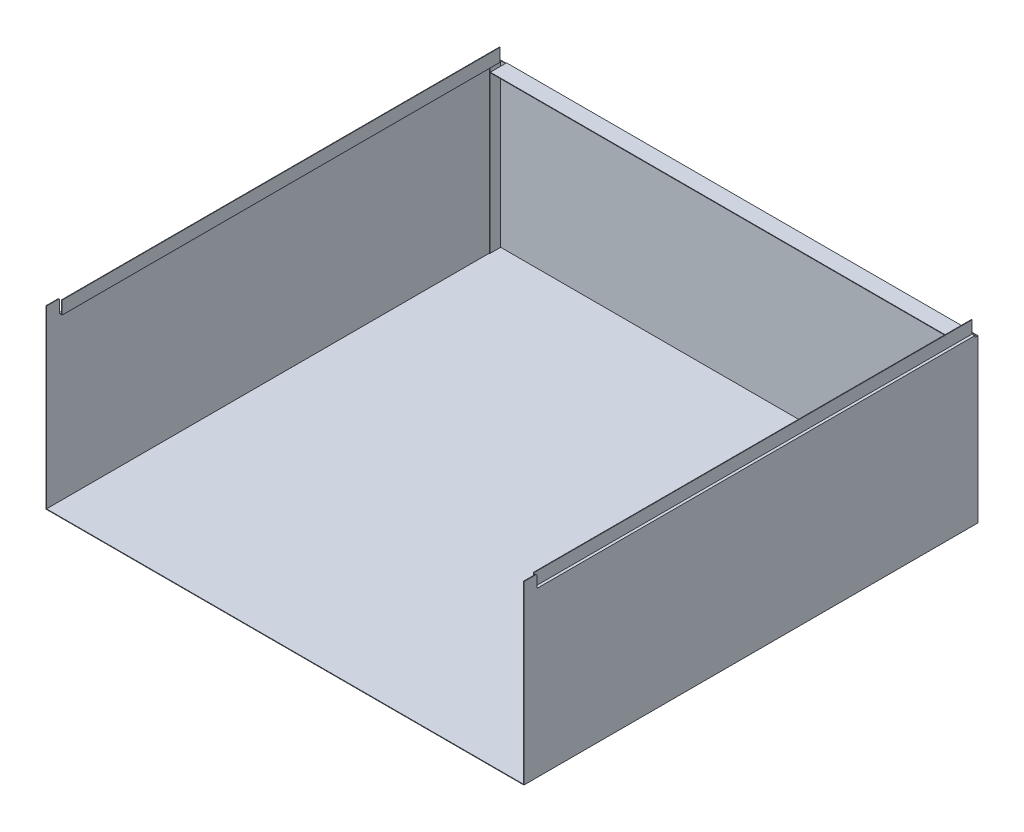
SolidWorks part; units mm, degrees
ref_plane "Front Plane" through (0, 0, 0) normal (0, 0, 1) x (1, 0, 0)
ref_plane "Top Plane" through (0, 0, 0) normal (0, 1, 0) x (1, 0, 0)
ref_plane "Right Plane" through (0, 0, 0) normal (1, 0, 0) x (0, 0, -1)
sketch "Sketch1" plane through (0, 0, 0) normal (0, 1, 0) x (1, 0, 0)
  line L1 (-221, 210) -> (221, 210)
  line L2 (-221, 210) -> (-221, -210)
  line L3 (-221, -210) -> (221, -210)
  line L4 (221, 210) -> (221, -210)
  line L5 (-221, 210) -> (221, -210) construction
  line L6 (-221, -210) -> (221, 210) construction
  point P0 (0, 0)
  dimension "D1" = 420
  dimension "D2" = 442
extrude "Boss-Extrude1" add sketch "Sketch1" along normal blind 0.5
sketch "Sketch2" plane through (0, 0.5, 0) normal (0, 1, 0) x (1, 0, 0)
  line L0 (221, 210) -> (-221, 210) construction
  line L1 (-221, -210) -> (-220.5, -210)
  line L2 (-221, -210) -> (-221, 210)
  line L3 (-221, 210) -> (-220.5, 210)
  line L4 (-220.5, -210) -> (-220.5, 210)
  line L5 (0, 0) -> (0, -210) construction
  line L6 (-221, -210) -> (221, -210) construction
  line L7 (220.5, -210) -> (220.5, 210)
  line L8 (221, 210) -> (220.5, 210)
  line L9 (221, -210) -> (221, 210)
  line L10 (221, -210) -> (220.5, -210)
  dimension "D1" = 0.5
extrude "Boss-Extrude2" add sketch "Sketch2" along normal blind 151
sketch "Sketch39" plane through (0, 0, -210) normal (0, 0, -1) x (-1, 0, 0)
  line L0 (220.5, 151) -> (218, 151)
  line L1 (218, 151) -> (218, 163)
  line L2 (218, 163) -> (218.5, 163)
  line L3 (218.5, 163) -> (218.5, 151.5)
  line L4 (218.5, 151.5) -> (220.5, 151.5)
  line L5 (220.5, 151.5) -> (220.5, 151)
  line L6 (-221, 0) -> (221, 0) construction
  line L7 (221, 151.5) -> (221, 0) construction
  line L8 (0, 0) -> (0, 165) construction
  line L9 (-220.5, 151.5) -> (-220.5, 151)
  line L10 (-218.5, 151.5) -> (-220.5, 151.5)
  line L11 (-218.5, 163) -> (-218.5, 151.5)
  line L12 (-218, 163) -> (-218.5, 163)
  line L13 (-218, 151) -> (-218, 163)
  line L14 (-220.5, 151) -> (-218, 151)
  line L15 (220.5, 151.5) -> (220.5, 0.5) construction
  dimension "D1" = 163
  dimension "D2" = 2.5
  dimension "D3" = 0.5
  dimension "D4" = 0.5
  dimension "D5" = 165
extrude "Boss-Extrude5" add sketch "Sketch39" against normal offset from surface (408 mm away) 12 up to face at (0, 75.875, 210)
sketch "Sketch7" plane through (0, 0.5, 0) normal (0, 1, 0) x (1, 0, 0)
  line L0 (220.5, 210) -> (220.5, -210) construction
  line L1 (-220.5, 210) -> (220.5, 210)
  line L3 (-220, 209.5) -> (220, 209.5)
  line L7 (220.5, 210) -> (220.5, 199.5)
  line L8 (220.5, 199.5) -> (220, 199.5)
  line L9 (220, 209.5) -> (220, 199.5)
  line L11 (-220.5, 210) -> (-220.5, 199.5)
  line L12 (-220.5, 199.5) -> (-220, 199.5)
  line L13 (-220, 209.5) -> (-220, 199.5)
  dimension "D1" = 0.5
  dimension "D2" = 0.5
  dimension "D3" = 10
  dimension "D4" = 0.5
extrude "Boss-Extrude3" add sketch "Sketch7" along normal offset from surface (149.5 mm away) 1 separate body up to face at (219.25, 151, -6)
sketch "Sketch41" plane through (0, 0, -210) normal (0, 0, -1) x (-1, 0, 0)
  line L0 (0, 0.5) -> (0, 150) construction
  line L1 (221, 150) -> (218, 150)
  line L2 (221, 150) -> (221, 163)
  line L3 (221, 163) -> (218, 163)
  line L4 (218, 150) -> (218, 163)
  line L5 (-220.5, 0.5) -> (220.5, 0.5) construction
  line L6 (220.5, 150) -> (-220.5, 150) construction
  line L7 (-218, 150) -> (-218, 163)
  line L8 (-221, 163) -> (-218, 163)
  line L9 (-221, 150) -> (-221, 163)
  line L10 (-221, 150) -> (-218, 150)
  line L11 (221, 151.5) -> (221, 0) construction
extrude "Cut-Extrude1" cut sketch "Sketch41" against normal blind 3
sketch "Sketch42" plane through (0, 150, 0) normal (0, 1, 0) x (1, 0, 0)
  line L0 (-220.5, 210) -> (220.5, 210) construction
  line L1 (-215, 210) -> (215, 210)
  line L2 (-215, 210) -> (-215, 209.5)
  line L3 (-215, 209.5) -> (215, 209.5)
  line L4 (215, 210) -> (215, 209.5)
  line L5 (220, 209.5) -> (-220, 209.5) construction
  point P8 (0, 210)
  dimension "D1" = 430
extrude "Boss-Extrude6" add sketch "Sketch42" against normal blind 147.4
sketch "Sketch43" plane through (0, 0, -210) normal (0, 0, 1) x (1, 0, 0)
  line L1 (-215, 150.5) -> (214.9987, 150.5)
  line L2 (-215, 150.5) -> (-215, 150)
  line L3 (-215, 150) -> (214.9987, 150)
  line L4 (214.9987, 150.5) -> (214.9987, 150)
  line L5 (220, 150) -> (-220, 150) construction
  dimension "D1" = 0.5
extrude "Boss-Extrude7" add sketch "Sketch43" along normal blind 15
sketch "Sketch44" plane through (0, 151.5, 0) normal (0, 1, 0) x (1, 0, 0)
  line L0 (-220.5, -210) -> (-220.5, -198) construction
  line L1 (-221, -210) -> (-220.5, -210)
  line L2 (-221, -210) -> (-221, -198)
  line L3 (-221, -198) -> (-220.5, -198)
  line L4 (-220.5, -210) -> (-220.5, -198)
  line L5 (220.5, -198) -> (220.5, -210) construction
  line L6 (221, -210) -> (220.5, -210)
  line L7 (221, -210) -> (221, -198)
  line L8 (221, -198) -> (220.5, -198)
  line L9 (220.5, -210) -> (220.5, -198)
  dimension "D1" = 12
extrude "Boss-Extrude8" add sketch "Sketch44" along normal up to surface (11.5 mm away) up to face at (-218.25, 163, -4.5)
fillet "Fillet1" radius 1 2 edges at (-220.75, 163, 198) (220.75, 163, 198)
fillet "Fillet2" radius 0.8 2 edges at (-220.75, 151.5, 198) (220.75, 151.5, 198)
equation "\"plateThickeness\"=0.5"
equation "\"D1@Sketch2\"=\"plateThickeness\""
equation "\"D1@Boss-Extrude1\"=\"plateThickeness\""
equation "\"D1@Sketch7\"=\"plateThickeness\""
equation "\"D2@Sketch7\"=\"plateThickeness\""
equation "\"D4@Sketch7\"=\"plateThickeness\""
equation "\"D1@Sketch43\"=\"plateThickeness\""
